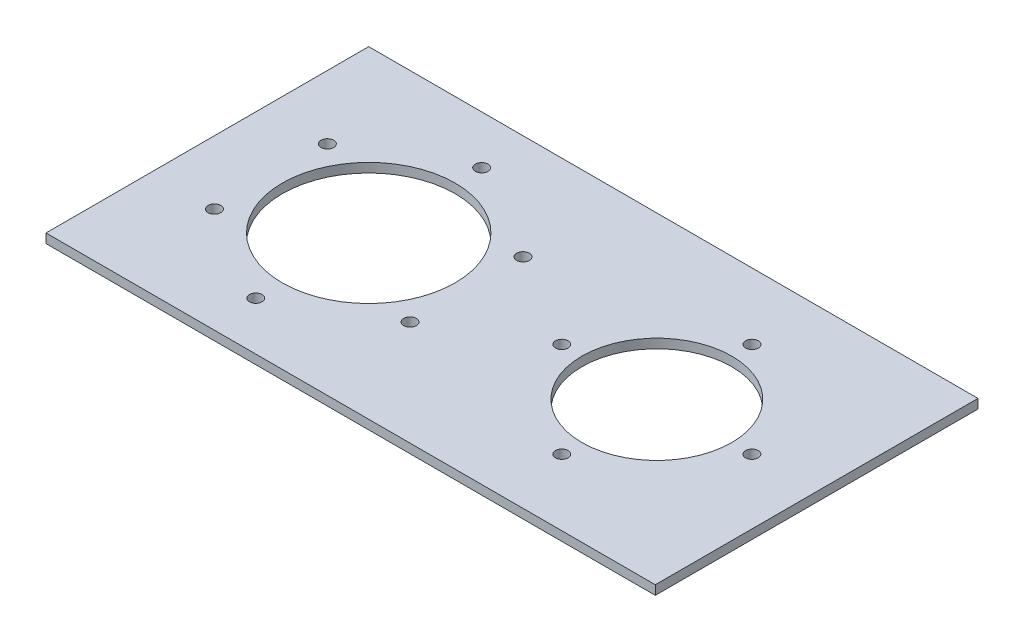
SolidWorks part; units mm, degrees
ref_plane "Front Plane" through (0, 0, 0) normal (0, 0, 1) x (1, 0, 0)
ref_plane "Top Plane" through (0, 0, 0) normal (0, 1, 0) x (1, 0, 0)
ref_plane "Right Plane" through (0, 0, 0) normal (1, 0, 0) x (0, 0, -1)
sketch "Sketch1" plane through (0, 0, 0) normal (0, 1, 0) x (1, 0, 0)
  line L1 (-140, -140) -> (388.6432, -140)
  line L2 (-140, -140) -> (-140, 140)
  line L3 (-140, 140) -> (388.6432, 140)
  line L4 (388.6432, -140) -> (388.6432, 140)
  circle A0 centre (0, 0) radius 75
  circle A1 centre (0, 0) radius 98 construction
  circle A2 centre (0, -98) radius 5.5
  circle A3 centre (-84.8705, -49) radius 5.5
  circle A4 centre (-84.8705, 49) radius 5.5
  circle A5 centre (0, 98) radius 5.5
  circle A6 centre (84.8705, 49) radius 5.5
  circle A7 centre (84.8705, -49) radius 5.5
  circle A8 centre (250, 0) radius 65
  circle A9 centre (250, 0) radius 82.5 construction
  circle A10 centre (332.5, 0) radius 5.5
  circle A11 centre (250, -82.5) radius 5.5
  circle A12 centre (167.5, 0) radius 5.5
  circle A13 centre (250, 82.5) radius 5.5
  point P4 (-140, 0)
  point P23 (0, 0)
  point P36 (250, 0)
  dimension "D2" = 150
  dimension "D3" = 196
  dimension "D4" = 11
  dimension "D8" = 130
  dimension "D9" = 165
  dimension "D10" = 11
  dimension "D1" = 280
  dimension "D6" = 140
  dimension "D7" = 250
  dimension "D5" = 6
  dimension "D11" = 4
extrude "Boss-Extrude1" add sketch "Sketch1" along normal blind 8
equation "\"d_ext_rouleau\"= 90"
equation "\"epaisseur_rouleau\"=80"
equation "\"alesage-rouleau\"= 52"
equation "\"jeu_dent_rouleau\"= 2"
equation "\"profondeur_dent_rouleau\"=4"
equation "\"n_dent_roueau\"= 15"
equation "\"d_ext_roulement_rouleau\"= 42"
equation "\"d_int_roulement_rouleau\"= 20"
equation "\"B_roulement_rouleau\"= 12"
equation "\"r_roulement_rouleau\"= 0.6"
equation "\"d_bille_roulement_rouleau\"= 8"
equation "\"F_anneau_alesage_rouleau\"=1.85"
equation "\"G_anneau_alesage_rouleau\"=47.5"
equation "\"K_anneau_alesage_rouleau\"=3.75"
equation "\"d_vis_flasque_rouleau\"=5"
equation "\"l-x_vis_flasque_rouleau\"=4"
equation "\"g_anneau_arbre_rouleau\"=19"
equation "\"f_anneau_arbre_rouleau\"=1.3"
equation "\"k_anneau_arbre_rouleau\"=1.5"
equation "\"entrax_vis_rouleau\"=65"
equation "\"d_granulat\"= 8"
equation "\"h_matrice\"= 18"
equation "\"d_matrice\"= 220"
equation "\"zone_vide_matrice\" = 48"
equation "\"d_alesage_matrice\"=20"
equation "\"a_clavette_alesage_matrice\"=6"
equation "\"B_roulement_matrice\"= 12"
equation "\"d_ext_roulement_matrice\"= 42"
equation "\"d_int_roulement_matrice\"= 20"
equation "\"r_roulement_matrice\"= 1"
equation "\"h_epaulement_arbre_matrice\" = 100"
equation "\"j_clavette_arbre_matrice\" = 6"
equation "\"g_anneaux_arbre_matrice\" = 16.2"
equation "\"f_anneaux_arbre_matrice\" = 1.1"
equation "\"B_roulement_bc_arbre_matrice\"= 10"
equation "\"e_anneaux_arbre_matrice\" = 1"
equation "\"h_polie_matrice\" = 40"
equation "\"l_arbre_matrice\" = 300"
equation "\"d_int_ecrou_encouch_matrice\" = 20"
equation "\"d_ext_ecrou_encouch_matrice\" = 32"
equation "\"b_ecrou_encouch_matrice\" = 6"
equation "\"s_ecrou_encouch_matrice\" = 4"
equation "\"G_ecrou_encouch_matrice\" = 1"
equation "\"E_ecrou_encouch_matrice\" = 4"
equation "\"d_int_roulement_conique_matrice\"=25"
equation "\"d_ext_roulement_conique_matrice\"=52"
equation "\"b_roulement_conique_matrice\"=16.25"
equation "\"d_int_roulement_bc_matrice\"=20"
equation "\"d_ext_roulement_bc_matrice\"=42"
equation "\"b_roulement_bc_matrice\"=12"
equation "\"d_tube_sup_carter\"=244.5"
equation "\"e_tube_sup_carter\"=12"
equation "\"d_tube_inf_catrer\"= 168.3"
equation "\"e_tube_inf_carter\"= 6"
equation "\"d_tube_inf_carter_cache\" = 244.5"
equation "\"e_tube_inf_carter_cache\" = 8"
equation "\"d_tube_sup_carter_cache\" = 133"
equation "\"e_tube_sup_carter_cache\" = 4"
equation "\"h_tube_trimee\" = 40"
equation "\"e_tole\" = 8"
equation "\"entraxe_vis_carter\" = 196"
equation "\"D3@Sketch1\"=\"entraxe_vis_carter\""
equation "\"d_vis_H_carter\"=10"
equation "\"entraxe_courroie\"=250"
equation "\"D7@Sketch1\"=\"entraxe_courroie\""
equation "\"D10@Sketch1\"=11"
